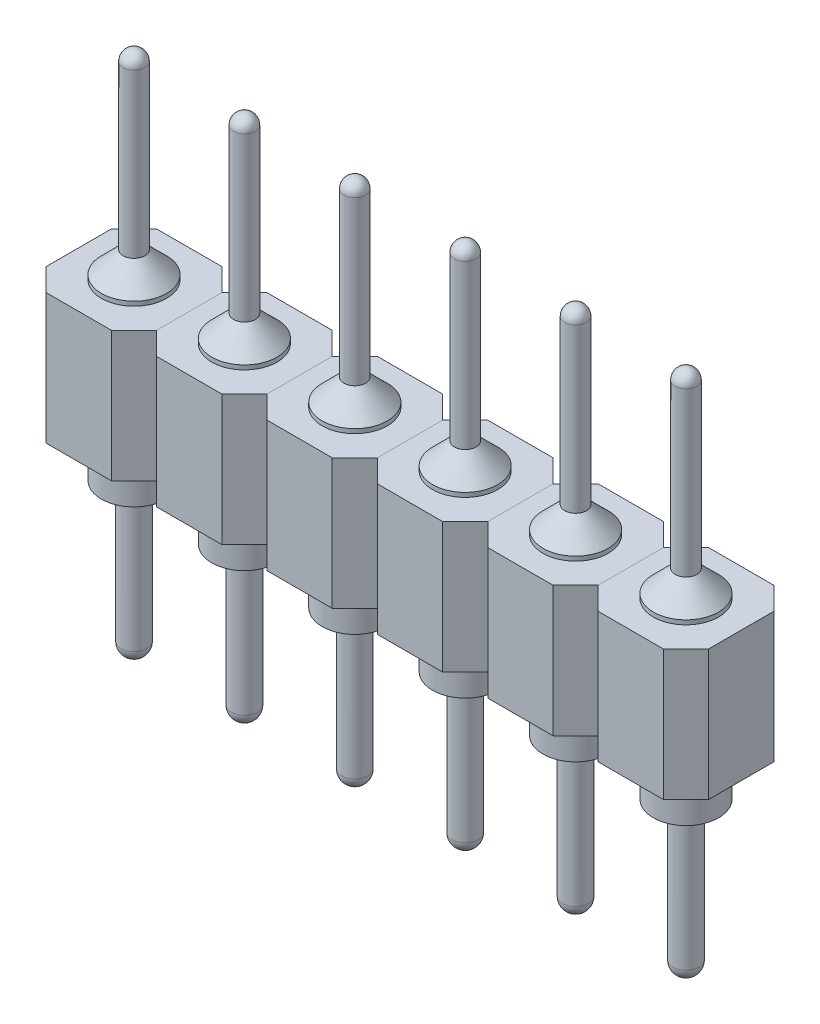
SolidWorks part; units mm, degrees
ref_plane "Спереди" through (0, 0, 0) normal (0, 0, 1) x (1, 0, 0)
ref_plane "Сверху" through (0, 0, 0) normal (0, 1, 0) x (1, 0, 0)
ref_plane "Справа" through (0, 0, 0) normal (1, 0, 0) x (0, 0, -1)
other "Configuration Table"
sketch "Эскиз2" plane through (0, 0, 0) normal (0, 0, 1) x (1, 0, 0)
  line L0 (0, 12.1) -> (0, 0) construction
  line L1 (0, 0) -> (0, 12.1)
  line L2 (0.3, 0.3) -> (0.3, 3.5)
  line L3 (0.3, 3.5) -> (0.75, 3.5)
  line L4 (0.75, 3.5) -> (0.75, 7.6)
  line L5 (0.25, 11.85) -> (0.25, 8.1)
  line L6 (0.25, 8.1) -> (0.75, 7.6)
  circle A0 centre (0, 11.85) radius 0.25
  circle A1 centre (0, 0.3) radius 0.3
  dimension "D1" = 0.5
  dimension "D2" = 0.6
  dimension "D3" = 4
  dimension "D4" = 0.5
  dimension "D5" = 4.1
  dimension "D6" = 3.5
  dimension "D7" = 0.75
revolve "Повернуть1" add sketch "Эскиз2" angle 360 about L1
sketch "Эскиз3" plane through (0, 3.5, 0) normal (0, -1, 0) x (1, 0, 0)
  line L0 (0, 1.27) -> (0, -1.27) construction
  line L1 (-0.75, 1.27) -> (0.75, 1.27)
  line L2 (-1.27, 0.75) -> (-1.27, -0.75)
  line L3 (-0.75, -1.27) -> (0.75, -1.27)
  line L4 (1.27, 0.75) -> (1.27, -0.75)
  line L5 (-1.27, 0.75) -> (-0.75, 1.27)
  line L6 (0.75, 1.27) -> (1.27, 0.75)
  line L7 (0.75, -1.27) -> (1.27, -0.75)
  line L8 (-1.27, -0.75) -> (-0.75, -1.27)
  circle A0 centre (0, 0) radius 0.75
  point P0 (-1.27, 1.27)
  point P1 (1.27, -1.27)
  point P2 (-1.27, -1.27)
  point P3 (1.27, 1.27)
  dimension "D2" = 1.5
  dimension "D1" = 2.54
  dimension "D3" = 2.54
extrude "Бобышка-Вытянуть1" add sketch "Эскиз3" against normal blind 3 from offset 1 separate body offset against normal yes
pattern_linear "Линейный массив1" count 6 spacing 2.54 along (-1, 0, 0) of bodies 104 103
